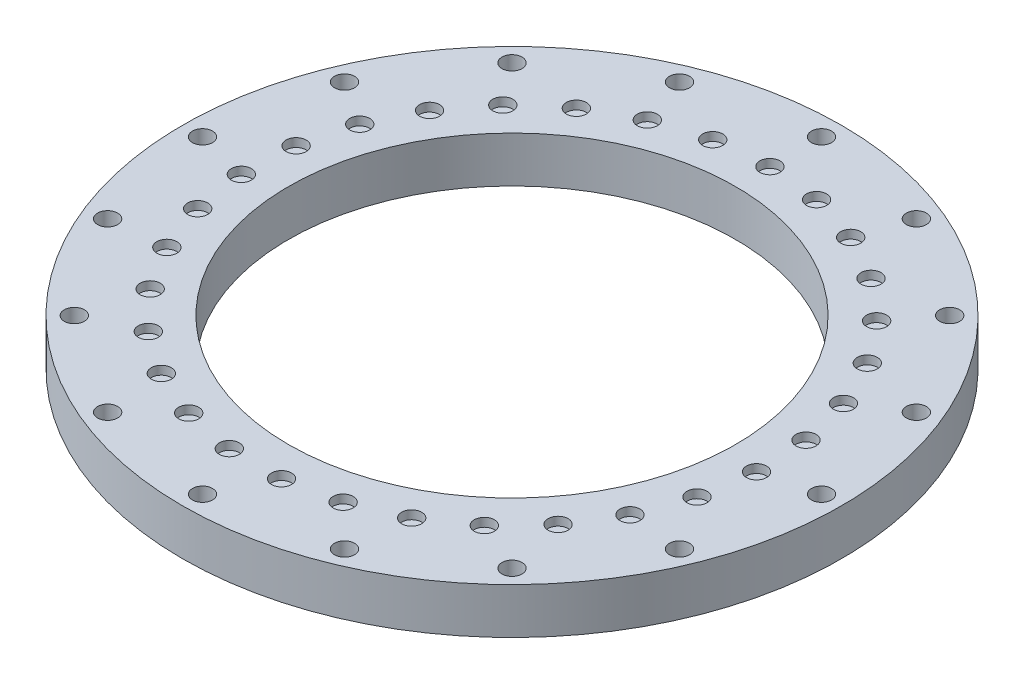
SolidWorks part; units mm, degrees
ref_plane "Front Plane" through (0, 0, 0) normal (0, 0, 1) x (1, 0, 0)
ref_plane "Top Plane" through (0, 0, 0) normal (0, 1, 0) x (1, 0, 0)
ref_plane "Right Plane" through (0, 0, 0) normal (1, 0, 0) x (0, 0, -1)
sketch "Sketch1" plane through (0, 0, 0) normal (0, 1, 0) x (1, 0, 0)
  circle A0 centre (0, 0) radius 57.5
  circle A1 centre (0, 0) radius 39
  dimension "D1" = 115
  dimension "D2" = 78
extrude "Boss-Extrude1" add sketch "Sketch1" along normal blind 8
sketch "Sketch2" plane through (0, 8, 0) normal (0, 1, 0) x (1, 0, 0)
  circle A0 centre (0, 0) radius 54 construction
  circle A1 centre (0, 54) radius 1.75
  circle A2 centre (20.6649, 49.8895) radius 1.75
  circle A3 centre (38.1838, 38.1838) radius 1.75
  circle A4 centre (49.8895, 20.6649) radius 1.75
  circle A5 centre (54, 0) radius 1.75
  circle A6 centre (49.8895, -20.6649) radius 1.75
  circle A7 centre (38.1838, -38.1838) radius 1.75
  circle A8 centre (20.6649, -49.8895) radius 1.75
  circle A9 centre (0, -54) radius 1.75
  circle A10 centre (-20.6649, -49.8895) radius 1.75
  circle A11 centre (-38.1838, -38.1838) radius 1.75
  circle A12 centre (-49.8895, -20.6649) radius 1.75
  circle A13 centre (-54, 0) radius 1.75
  circle A14 centre (-49.8895, 20.6649) radius 1.75
  circle A15 centre (-38.1838, 38.1838) radius 1.75
  circle A16 centre (-20.6649, 49.8895) radius 1.75
  point P37 (0, 0)
  dimension "D1" = 108
  dimension "D2" = 3.5
  dimension "D3" = 16
extrude "Cut-Extrude1" cut sketch "Sketch2" against normal blind 17
sketch "Sketch3" plane through (0, 8, 0) normal (0, 1, 0) x (1, 0, 0)
  circle A0 centre (0, 0) radius 45 construction
  circle A1 centre (0, 45) radius 1.75
  circle A2 centre (9.0584, 44.0788) radius 1.75
  circle A3 centre (17.746, 41.3531) radius 1.75
  circle A4 centre (25.7071, 36.9344) radius 1.75
  circle A5 centre (32.6157, 31.0035) radius 1.75
  circle A6 centre (38.189, 23.8034) radius 1.75
  circle A7 centre (42.1988, 15.6287) radius 1.75
  circle A8 centre (44.4811, 6.8142) radius 1.75
  circle A9 centre (44.9422, -2.2792) radius 1.75
  circle A10 centre (43.5635, -11.2794) radius 1.75
  circle A11 centre (40.4012, -19.8177) radius 1.75
  circle A12 centre (35.5849, -27.5448) radius 1.75
  circle A13 centre (29.3118, -34.1441) radius 1.75
  circle A14 centre (21.8386, -39.3456) radius 1.75
  circle A15 centre (13.4713, -42.9363) radius 1.75
  circle A16 centre (4.5526, -44.7691) radius 1.75
  circle A17 centre (-4.5526, -44.7691) radius 1.75
  circle A18 centre (-13.4713, -42.9363) radius 1.75
  circle A19 centre (-21.8386, -39.3456) radius 1.75
  circle A20 centre (-29.3118, -34.1441) radius 1.75
  circle A21 centre (-35.5849, -27.5448) radius 1.75
  circle A22 centre (-40.4012, -19.8177) radius 1.75
  circle A23 centre (-43.5635, -11.2794) radius 1.75
  circle A24 centre (-44.9422, -2.2792) radius 1.75
  circle A25 centre (-44.4811, 6.8142) radius 1.75
  circle A26 centre (-42.1988, 15.6287) radius 1.75
  circle A27 centre (-38.189, 23.8034) radius 1.75
  circle A28 centre (-32.6157, 31.0035) radius 1.75
  circle A29 centre (-25.7071, 36.9344) radius 1.75
  circle A30 centre (-17.746, 41.3531) radius 1.75
  circle A31 centre (-9.0584, 44.0788) radius 1.75
  point P67 (0, 0)
  dimension "D1" = 90
  dimension "D2" = 3.5
  dimension "D3" = 31
extrude "Cut-Extrude2" cut sketch "Sketch3" against normal blind 1.5
sketch "Sketch4" plane through (0, 0, 0) normal (0, -1, 0) x (1, 0, 0)
  circle A0 centre (0, 0) radius 50
  dimension "D1" = 100
sketch "Sketch5" plane through (0, 0, 0) normal (0, -1, 0) x (1, 0, 0)
  line L0 (0, 45) -> (0, 0) construction
  line L4 (0, 0) -> (26.5522, 0) construction
  circle A0 centre (0, 45) radius 2
  circle A1 centre (0, 0) radius 45 construction
  circle A2 centre (38.9711, -22.5) radius 2
  circle A3 centre (-38.9711, -22.5) radius 2
  point P11 (0, 0)
  dimension "D1" = 90
  dimension "D2" = 4
  dimension "D4" = 90
  dimension "D3" = 3
extrude "Cut-Extrude3" cut sketch "Sketch5" against normal blind 5
